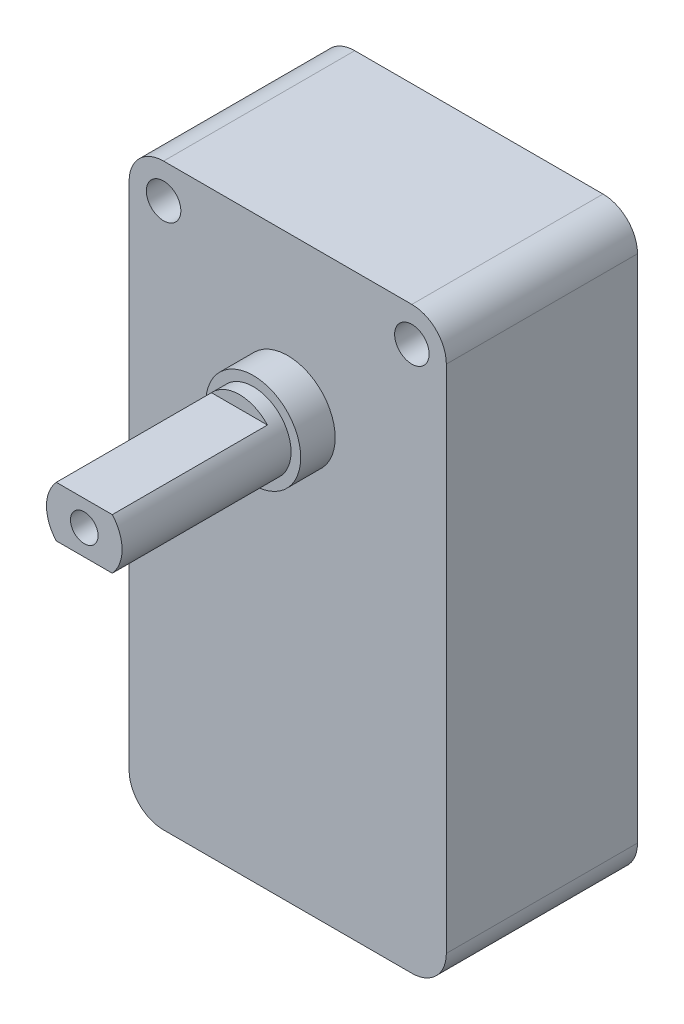
SolidWorks part; units mm, degrees
ref_plane "Front Plane" through (0, 0, 0) normal (0, 0, 1) x (1, 0, 0)
ref_plane "Top Plane" through (0, 0, 0) normal (0, 1, 0) x (1, 0, 0)
ref_plane "Right Plane" through (0, 0, 0) normal (1, 0, 0) x (0, 0, -1)
sketch "Sketch1" plane through (0, 0, 0) normal (0, 0, 1) x (1, 0, 0)
  line L0 (-23.4804, 0) -> (61.8711, 0) construction
  line L1 (-9, 11.15) -> (9, 11.15)
  line L2 (-11.5, 8.65) -> (-11.5, -28.35)
  line L3 (-9, -30.85) -> (9, -30.85)
  line L4 (11.5, 8.65) -> (11.5, -28.35)
  line L5 (0, 48.9175) -> (0, -54.6191) construction
  line L6 (2.0303, 1.84) -> (-2.0303, 1.84)
  line L7 (-2.0303, -1.84) -> (2.0303, -1.84)
  circle A0 centre (0, 0) radius 3.44
  circle A1 centre (0, 0) radius 2.74
  arc A2 (9, 11.15) -> (11.5, 8.65) centre (9, 8.65) cw
  circle A3 centre (-9, 8.65) radius 1.25
  arc A4 (9, -30.85) -> (11.5, -28.35) centre (9, -28.35) ccw
  arc A5 (-11.5, -28.35) -> (-9, -30.85) centre (-9, -28.35) ccw
  arc A6 (-9, 11.15) -> (-11.5, 8.65) centre (-9, 8.65) ccw
  circle A7 centre (9, 8.65) radius 1.25
  circle A8 centre (0, 0) radius 1
  point P20 (11.5, 11.15)
  point P27 (-11.5, 11.15)
  dimension "D3" = 6.88
  dimension "D4" = 5.48
  dimension "D7" = 2.5
  dimension "D8" = 2.5
  dimension "D9" = 2
  dimension "D1" = 42
  dimension "D2" = 23
  dimension "D5" = 3.68
  dimension "D6" = 11.15
extrude "Boss-Extrude1" add sketch "Sketch1" against normal blind 13.86 contours L1 A6 L2 A5 L3 A4 L4 A2 A7 A0 A3 | A0 region at (0, -10.4496, 0)
extrude "Boss-Extrude2" add sketch "Sketch1<3>" along normal blind 2.5 contours A0
sketch "Sketch1<3>" plane through (0, 0, 0) normal (0, 0, 1) x (1, 0, 0) same geometry as "Sketch1"
extrude "Boss-Extrude3" add sketch "Sketch1<4>" along normal blind 3.5 contours A1
sketch "Sketch1<4>" plane through (0, 0, 0) normal (0, 0, 1) x (1, 0, 0) same geometry as "Sketch1"
extrude "Boss-Extrude4" add sketch "Sketch1<5>" along normal blind 14.75 contours L6 A1 L7 region at (2.4948, 0.9623, 0)
sketch "Sketch1<5>" plane through (0, 0, 0) normal (0, 0, 1) x (1, 0, 0) same geometry as "Sketch1"
